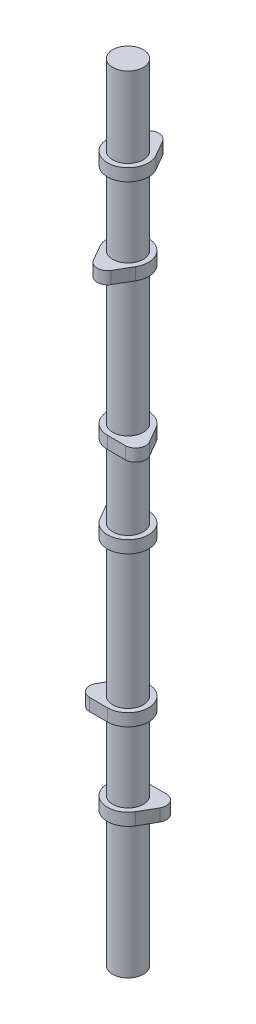
SolidWorks part; units mm, degrees
ref_plane "Front Plane" through (0, 0, 0) normal (0, 0, 1) x (1, 0, 0)
ref_plane "Top Plane" through (0, 0, 0) normal (0, 1, 0) x (1, 0, 0)
ref_plane "Right Plane" through (0, 0, 0) normal (1, 0, 0) x (0, 0, -1)
sketch "Sketch1" plane through (0, 0, 0) normal (0, 1, 0) x (1, 0, 0)
  line L0 (-5.4993, 15.875) -> (-10.9985, 6.35)
  line L1 (5.4993, 15.875) -> (10.9985, 6.35)
  arc A0 (-10.9985, 6.35) -> (10.9985, 6.35) centre (0, 0) ccw
  arc A1 (5.4993, 15.875) -> (-5.4993, 15.875) centre (0, 12.7) ccw
  dimension "D2" = 12.7
  dimension "D3" = 25.4
  dimension "D1" = 12.7
extrude "Boss-Extrude1" add sketch "Sketch1" along normal blind 7.62
ref_axis "Axis1" through (0, 7.62, 0) along (0, -1, 0)
pattern_linear "LPattern2" count 2 spacing 53.34 along (0, -1, 0) of bodies 101
move or copy body "Body-Move/Copy1" bodies to move or copy 103 copy no rotation origin (0, 0, 0) rotation axis (0, 1, 0) rotation angle 180
pattern_linear "LPattern3" count 3 spacing 146.05 along (0, -1, 0) of bodies 101 104
move or copy body "Body-Move/Copy2" bodies to move or copy 105 107 copy no rotation origin (0, 0, 0) rotation axis (0, -1, 0) rotation angle 120
move or copy body "Body-Move/Copy3" bodies to move or copy 106 108 copy no rotation origin (0, 0, 0) rotation axis (0, 1, 0) rotation angle 120
sketch "Sketch2" plane through (0, 0, 0) normal (0, 1, 0) x (1, 0, 0)
  circle A0 centre (0, 0) radius 9.5
  dimension "D1" = 19
extrude "Boss-Extrude2" add sketch "Sketch2" against normal blind 486.09 from offset 57.15
